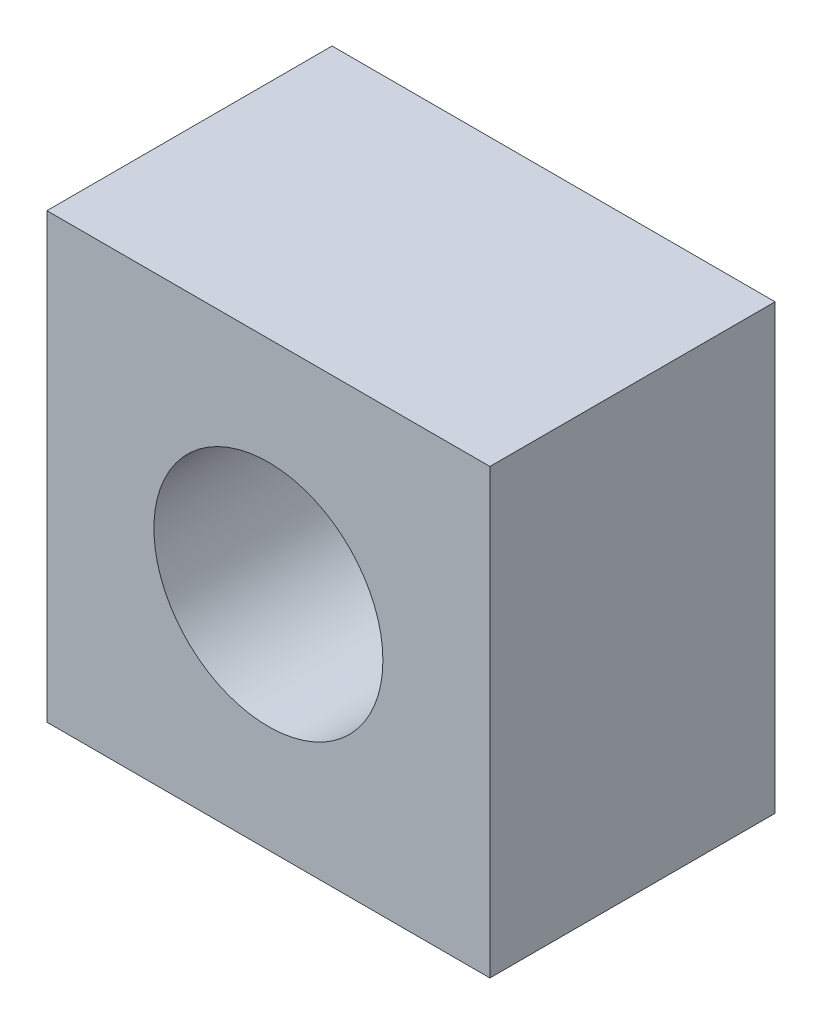
SolidWorks part; units mm, degrees
ref_plane "Front Plane" through (0, 0, 0) normal (0, 0, 1) x (1, 0, 0)
ref_plane "Top Plane" through (0, 0, 0) normal (0, 1, 0) x (1, 0, 0)
ref_plane "Right Plane" through (0, 0, 0) normal (1, 0, 0) x (0, 0, -1)
sketch "Sketch1" plane through (0, 0, 0) normal (0, 0, 1) x (1, 0, 0)
  line L0 (0, 0) -> (3, 0)
  line L1 (55, 0) -> (-55, 0) construction
  line L3 (3, 0) -> (7, 0)
  line L5 (7, 0) -> (8, 0)
  line L6 (8, 0) -> (8, 8)
  line L7 (8, 8) -> (0, 8)
  line L8 (0, -55) -> (0, 55) construction
  line L9 (0, 8) -> (0, 0)
  dimension "D1" = 8
  dimension "D4" = 8
extrude "Boss-Extrude1" add sketch "Sketch1" along normal blind 5.15
sketch "Sketch2" plane through (0, 0, 5.15) normal (0, 0, 1) x (1, 0, 0)
  line L0 (0, 0) -> (8, 0) construction
  line L1 (4, 0) -> (4, 8) construction
  line L2 (8, 8) -> (0, 8) construction
  circle A0 centre (4, 4) radius 2.0675
  point P2 (4, 0)
  dimension "D1" = 4
extrude "Cut-Extrude1" cut sketch "Sketch2" against normal through all
